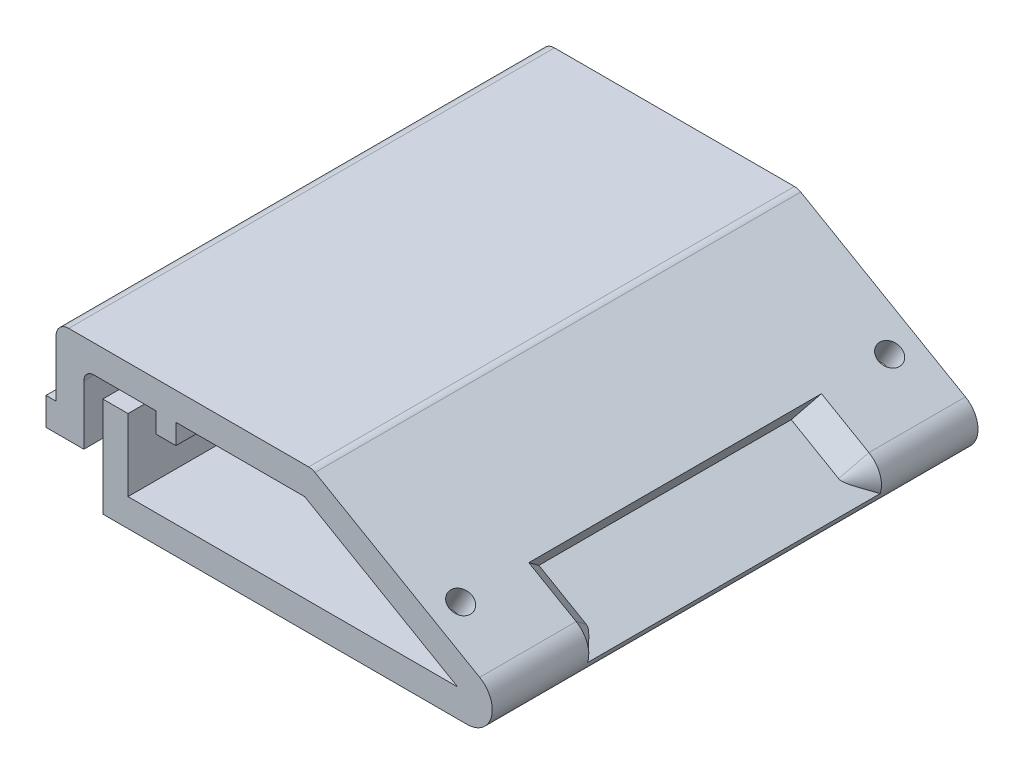
SolidWorks part; units mm, degrees
material "ABS_eSun_GRN"
ref_plane "Front Plane" through (0, 0, 0) normal (0, 0, 1) x (1, 0, 0)
ref_plane "Top Plane" through (0, 0, 0) normal (0, 1, 0) x (1, 0, 0)
ref_plane "Right Plane" through (0, 0, 0) normal (1, 0, 0) x (0, 0, -1)
sketch "Sketch1" plane through (0, 0, 0) normal (0, 0, 1) x (1, 0, 0)
  line L0 (12, -5.5) -> (9, -5.5)
  line L1 (13.5, -7) -> (41.6244, -7)
  line L2 (17.5, -7) -> (17.5, 0) construction
  line L4 (17.5, 0) -> (28.7583, 0) construction
  line L5 (17.5, 0) -> (29.5, 0)
  line L6 (0, 0) -> (0, -7) construction
  line L7 (12, 0) -> (17.5, 0)
  line L8 (12, 0) -> (12, -5.5)
  line L9 (0, -50) -> (0, 50) construction
  line L10 (29.5, 0) -> (41.6244, -7)
  dimension "D1" = 5.5
  dimension "D2" = 30
  dimension "D3" = 1.5
  dimension "D4" = 7
  dimension "D5" = 1.5
  dimension "D6" = 35
  dimension "D7" = 12
  dimension "D8" = 3
extrude "Extrude-Thin1" add sketch "Sketch1" along normal mid plane 38.5 thin
fillet "Fillet1" radius 2 1 edges at (49.8349, -9.2, 0)
fillet "Fillet2" radius 1 2 edges at (9.8, 2.2, 0) (30.0895, 2.2, 0)
sketch "Sketch2" plane through (8.475, 14.6791, 0) normal (0.5, 0.866, 0) x (0.866, -0.5, 0)
  line L0 (35.9583, 17) -> (35.9583, -17) construction
  line L2 (24.9583, -19.25) -> (24.9583, 19.25) construction
  circle A0 centre (35.9583, 17) radius 0.9
  circle A1 centre (35.9583, -17) radius 0.9
  point P4 (35.9583, 0)
  dimension "D1" = 1.8
  dimension "D2" = 34
  dimension "D3" = 11
extrude "Cut-Extrude1" cut sketch "Sketch2" against normal up to next
sketch "Sketch3" plane through (0, 0, 0) normal (0, 0, 1) x (1, 0, 0)
  line L0 (41.6244, -7) -> (13.5, -7) construction
  line L1 (15.5, -7) -> (13.5, -7)
  line L2 (15.5, -7) -> (15.5, -1.3)
  line L3 (15.5, -1.3) -> (13.5, -1.3)
  line L4 (13.5, -7) -> (13.5, -1.3)
  line L6 (13.5, -9.2) -> (13.5, -7) construction
  line L7 (12, 0) -> (29.5, 0) construction
  line L8 (17.7, 0) -> (19.3, 0)
  line L9 (17.7, 0) -> (17.7, -1.6)
  line L10 (17.7, -1.6) -> (19.3, -1.6)
  line L11 (19.3, 0) -> (19.3, -1.6)
  line L12 (0, 0) -> (0, 4.9669) construction
  line L13 (0, -50) -> (0, 50) construction
  dimension "D1" = 1.3
  dimension "D2" = 2
  dimension "D4" = 1.6
  dimension "D5" = 35.4
extrude "Boss-Extrude1" add sketch "Sketch3" along normal mid plane 38.5
sketch "Sketch9" plane through (8.475, 14.6791, 0) normal (0.5, 0.866, 0) x (0.866, -0.5, 0)
  line L1 (42.2942, 10) -> (35.9583, 10)
  line L2 (42.2942, 10) -> (42.2942, -10)
  line L3 (42.2942, -10) -> (35.9583, -10)
  line L4 (35.9583, 10) -> (35.9583, -10)
  line L5 (42.2942, -19.25) -> (42.2942, 19.25) construction
  point P6 (35.9583, 17)
  point P9 (35.9583, 0)
  dimension "D1" = 20
extrude "Cut-Extrude4" cut sketch "Sketch9" against normal blind 1.6
chamfer "Chamfer2" distance 1.6 angle 45 4 edges at (44.2408, -6.4908, -10) (41.4933, -4.384, -10) (44.2408, -6.4908, 10) (41.4933, -4.384, 10)
sketch "Sketch10" plane through (0, -9.2, 0) normal (0, -1, 0) x (1, 0, 0)
  line L0 (42.3708, -19.25) -> (13.5, -19.25) construction
  text T0 "v3"
  dimension "D1" = 6
extrude "VERSION" cut sketch "Sketch10" against normal blind 0.5
fillet "Fillet3" radius 0.8 1 edges at (12, 0, 0)
equation "\"width\"= 38.5"
equation "\"D1@Extrude-Thin1\"=\"width\""
equation "\"D1@Boss-Extrude1\"=\"width\""
equation "\"tooth_width\"=10"
